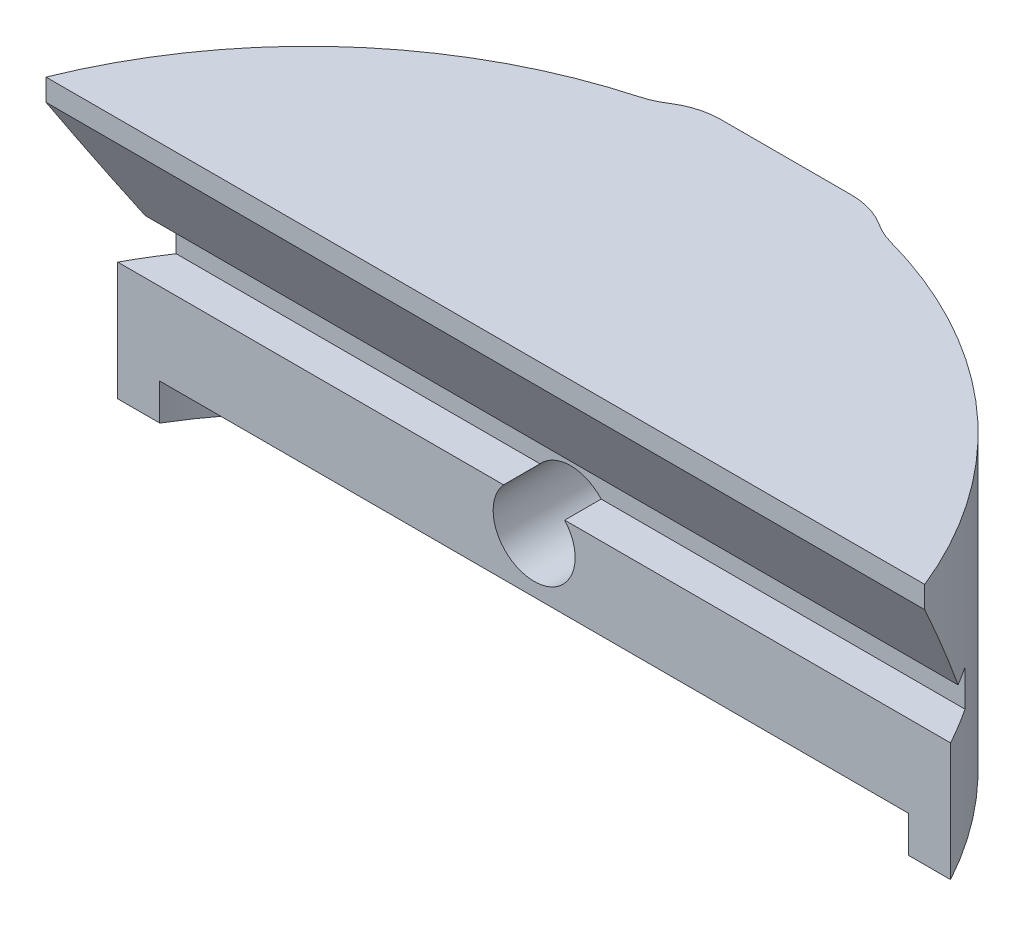
SolidWorks part; units mm, degrees
material "3.1355 (EN-AW 2024)"
ref_plane "Спереди" through (0, 0, 0) normal (0, 0, 1) x (1, 0, 0)
ref_plane "Сверху" through (0, 0, 0) normal (0, 1, 0) x (1, 0, 0)
ref_plane "Справа" through (0, 0, 0) normal (1, 0, 0) x (0, 0, -1)
sketch "Эскиз1" plane through (0, 0, 0) normal (0, 1, 0) x (1, 0, 0)
  circle A0 centre (0, 0) radius 26
  dimension "D1" = 52
extrude "Бобышка-Вытянуть1" add sketch "Эскиз1" along normal blind 14
sketch "Эскиз2" plane through (0, 0, 0) normal (1, 0, 0) x (0, 0, -1)
  line L0 (0, 14) -> (0, 0) construction
  line L1 (26, 14) -> (-26, 14) construction
  line L2 (13.6547, 6) -> (-13.6547, 6)
  line L3 (-13.6547, 6) -> (-9.7287, 12.8)
  line L4 (-9.7287, 12.8) -> (-9.7287, 14)
  line L5 (-9.7287, 14) -> (9.7287, 14)
  line L6 (0, 14) -> (0, 6) construction
  line L7 (13.6547, 6) -> (9.7287, 12.8)
  line L8 (9.7287, 12.8) -> (9.7287, 14)
  line L9 (-12.5, 8) -> (-12.5, 6) construction
  dimension "D1" = 8
  dimension "D2" = 1.2
  dimension "D3" = 60
  dimension "D4" = 13.6547
  dimension "D5" = 9.7287
  dimension "D6" = 2
  dimension "D7" = 12.5
extrude "Вырез-Вытянуть1" cut sketch "Эскиз2" against normal mid plane 60
sketch "Примерка" plane through (0, 0, 0) normal (1, 0, 0) x (0, 0, -1)
  line L0 (13.6547, 6) -> (-13.6547, 6) construction
  line L1 (-12.5, 14) -> (12.5, 14)
  line L2 (-12.5, 14) -> (-12.5, 6)
  line L3 (-12.5, 6) -> (12.5, 6)
  line L4 (12.5, 14) -> (12.5, 6)
  point P6 (0, 6)
  dimension "D1" = 8
  dimension "D2" = 25
sketch "Эскиз5" plane through (0, 0, 0) normal (0, -1, 0) x (1, 0, 0)
  line L2 (-22.1258, -15.6547) -> (22.1258, -15.6547)
  line L3 (-18.1915, -15.6547) -> (18.1915, -15.6547)
  circle A2 centre (0, 0) radius 24
  arc A3 (-18.1915, -15.6547) -> (18.1915, -15.6547) centre (0, 0) ccw
  dimension "D1" = 2
  dimension "D2" = 2
sketch "Эскиз6" plane through (0, 6, 0) normal (0, 1, 0) x (1, 0, 0)
  line L1 (18.4208, 0) -> (-15.4735, 0) construction
  circle A0 centre (0, 0) radius 6 construction
  circle A1 centre (0, 0) radius 12.5 construction
  dimension "D1" = 12
  dimension "D2" = 25
hole_wizard "Цековка для винта с внутренним шестигранником M32" positions "Эскиз14" profile "Эскиз13" counterbore size "M3" standard "Ansi Metric" end condition up to next
sketch "Эскиз14" plane through (0, 6, 0) normal (0, 1, 0) x (1, 0, 0)
  line L0 (18.4208, 0) -> (-15.4735, 0) construction
  circle A0 centre (0, 0) radius 12.5 construction
  circle A1 centre (0, 0) radius 6 construction
  point P0 (-12.5, 0)
  point P6 (12.5, 0)
  point P20 (-6, 0)
  point P24 (6, 0)
sketch "Эскиз13" plane through (-12.5, 6, 0) normal (1, 0, 0) x (0, 0, 1)
  line L0 (0, 0) -> (0, 6)
  line L1 (0, 6) -> (1.7, 6)
  line L3 (1.7, 6) -> (1.7, 3)
  line L4 (1.7, 3) -> (3.3, 3)
  line L5 (3.3, 3) -> (3.3, 0)
  line L7 (3.3, 0) -> (0, 0)
  line L11 (0, -6.35) -> (0, 107.95) construction
  dimension "Диаметр сквозного отверстия" = 3.4
  dimension "Глубина сквозного отверстия" = 6
  dimension "Диаметр цековки" = 6.6
  dimension "Глубина цековки" = 3
sketch "Эскиз12" plane through (0, 0, 0) normal (0, -1, 0) x (1, 0, 0)
  circle A0 centre (0, 0) radius 26 construction
  circle A1 centre (0, 0) radius 26
  circle A3 centre (0, 0) radius 24
  dimension "D1" = 2
extrude "Бобышка-Вытянуть2" add sketch "Эскиз12" along normal blind 2
sketch "Эскиз17" plane through (0, 14, 0) normal (0, 1, 0) x (1, 0, 0)
  line L0 (-24.1112, -9.7287) -> (24.1112, -9.7287) construction
  line L1 (-24.1112, -9.7287) -> (24.1112, -9.7287)
  arc A0 (-24.1112, -9.7287) -> (24.1112, -9.7287) centre (0, 0) ccw construction
  arc A1 (-24.1112, -9.7287) -> (24.1112, -9.7287) centre (0, 0) ccw
extrude "Вырез-Вытянуть4" cut sketch "Эскиз17" against normal up to surface (8 mm away) up to face at (9.25, 6, 0)
fillet "Скругление2" radius 1 4 edges at (9.25, 4.5, -0.5723) (9.25, 4.5, 0.5723) (-9.25, 4.5, 0.5723) (-9.25, 4.5, -0.5723)
sketch "Эскиз18" plane through (0, 0, 0) normal (0, -1, 0) x (1, 0, 0)
  circle A0 centre (0, 0) radius 6
extrude "Вырез-Вытянуть5" cut sketch "Эскиз18" against normal blind 3
sketch "Эскиз19" plane through (0, 6, 0) normal (0, 1, 0) x (1, 0, 0)
  line L0 (-22.3137, -13.3453) -> (22.3137, -13.3453)
  line L1 (-22.1258, 13.6547) -> (22.1258, 13.6547) construction
  arc A0 (-22.1258, 13.6547) -> (22.1258, 13.6547) centre (0, 0) ccw construction
  arc A1 (-22.3137, -13.3453) -> (22.3137, -13.3453) centre (0, 0) ccw
  dimension "D1" = 27
extrude "Вырез-Вытянуть6" cut sketch "Эскиз19" against normal blind 10
sketch "Эскиз21" plane through (0, 0, 13.3453) normal (0, 0, 1) x (1, 0, 0)
  line L0 (0, 0) -> (0, 6) construction
  line L1 (19.9475, 0) -> (-19.9475, 0) construction
  line L2 (22.3137, 6) -> (-22.3137, 6) construction
hole_wizard "Отверстие обработанное метчиком M4x0.71" positions "Эскиз23" profile "Эскиз22" tap size "M4x0.7" standard "Ansi Metric"
sketch "Эскиз23" plane through (0, 0, 13.3453) normal (0, 0, 1) x (1, 0, 0)
  line L0 (0, 0) -> (0, 6) construction
  point P0 (0, 3)
sketch "Эскиз22" plane through (0, 3, 13.3453) normal (1, 0, 0) x (0, -1, 0)
  line L0 (0, 0) -> (0, 12.4914)
  line L1 (0, 12.4914) -> (1.65, 11.5)
  line L2 (1.65, 11.5) -> (1.65, 0)
  line L5 (1.65, 0) -> (0, 0)
  line L10 (0, 12.4914) -> (-1.65, 11.5) construction
  line L11 (0, -6.35) -> (0, 107.95) construction
  dimension "Диаметр сверла" = 3.3
  dimension "Глубина сверла" = 11.5
  dimension "Угол заточки сверла" = 118
cosmetic thread "Отверстие резьбы1" parameters "D1"=8, "D2"=4
sketch "Эскиз20" plane through (0, 0, 13.3453) normal (0, 0, 1) x (1, 0, 0)
  line L0 (0, 3.1198) -> (0, -5.6063) construction
  line L1 (22.3137, 6) -> (-22.3137, 6) construction
  line L2 (-25.2658, 5) -> (25.2658, 5)
  line L3 (-25.2658, 5) -> (-25.2658, -2)
  line L4 (-25.2658, -2) -> (25.2658, -2)
  line L5 (25.2658, 5) -> (25.2658, -2)
  line L6 (-25.2658, 5) -> (25.2658, -2) construction
  line L7 (-25.2658, -2) -> (25.2658, 5) construction
  line L8 (-22.3137, -2) -> (-19.9475, -2) construction
  point P3 (0, 1.5)
  dimension "D1" = 1
extrude "Вырез-Вытянуть7" cut sketch "Эскиз20" against normal blind 2
sketch "Эскиз24" plane through (0, 0, 11.3453) normal (0, 0, 1) x (1, 0, 0)
  line L0 (0, 0) -> (0, -5.889) construction
  line L1 (-21.1491, 0) -> (21.1491, 0) construction
  line L2 (-11.3153, 1) -> (11.3153, 1)
  line L3 (-11.3153, 1) -> (-11.3153, 0)
  line L4 (-11.3153, 0) -> (11.3153, 0)
  line L5 (11.3153, 1) -> (11.3153, 0)
  line L6 (-11.3153, 1) -> (11.3153, 0) construction
  line L7 (-11.3153, 0) -> (11.3153, 1) construction
  point P3 (0, 0.5)
  dimension "D1" = 1
extrude "Бобышка-Вытянуть3" add sketch "Эскиз24" along normal blind 2
ref_plane "Плоскость1" through (26, 0, 0) normal (1, 0, 0) x (0, 0, -1)
sketch "Эскиз25" plane through (26, 0, 0) normal (1, 0, 0) x (0, 0, -1)
  line L0 (13.6547, 6) -> (13.6547, -5.3122) construction
  line L1 (12.4047, -5.3122) -> (-15.3444, -5.3122)
  line L2 (-15.3444, -5.3122) -> (-15.3444, 6)
  line L3 (-15.3444, 6) -> (12.4047, 6)
  line L4 (12.4047, 6) -> (12.4047, -5.3122)
  line L5 (13.6547, 6) -> (-13.3453, 6) construction
  dimension "D1" = 2.5
extrude "Вырез-Вытянуть8" cut sketch "Эскиз25" against normal through all
sketch "Эскиз26" plane through (26, 0, 0) normal (1, 0, 0) x (0, 0, -1)
  line L0 (12.4047, 6.5) -> (14.4047, 6.5)
  line L1 (14.4047, 6.5) -> (14.4047, 4.5)
  line L2 (14.4047, 4.5) -> (12.4047, 4.5)
  line L3 (12.4047, 4.5) -> (12.4047, 6.5)
  line L5 (26, 14) -> (9.7287, 14) construction
  line L7 (12.4047, 6) -> (12.4047, -2) construction
  dimension "D1" = 2
  dimension "D2" = 7.5
  dimension "D3" = 2
extrude "Вырез-Вытянуть10" cut sketch "Эскиз26" against normal through all
sketch "Эскиз27" plane through (0, 14, 0) normal (0, 1, 0) x (1, 0, 0)
  line L0 (0, 26) -> (0, 26.4574) construction
  line L2 (24.1112, 9.7287) -> (-24.1112, 9.7287) construction
  line L3 (-5, 26.2287) -> (5, 26.2287)
  line L4 (-5, 26.2287) -> (-5, 25.5147)
  line L6 (5, 26.2287) -> (5, 25.5147)
  line L7 (-5, 26.2287) -> (5.2086, 22.8067) construction
  line L8 (-6.2536, 22.4564) -> (5, 26.2287) construction
  arc A0 (-5, 25.5147) -> (5, 25.5147) centre (0, 0) cw
  arc A1 (24.1112, 9.7287) -> (-24.1112, 9.7287) centre (0, 0) ccw construction
  point P5 (0, 24.5527)
  point P18 (0, 26.2287)
  dimension "D1" = 10
  dimension "D2" = 16.5
extrude "Бобышка-Вытянуть5" add sketch "Эскиз27" against normal up to surface (16 mm away) up to face at (0, -2, -18.7024)
fillet "Скругление3" radius 4 2 edges at (5, 6, -25.5147) (-5, 6, -25.5147)
fillet "Скругление4" radius 4 2 edges at (5, 6, -26.2287) (-5, 6, -26.2287)
sketch "Эскиз28" plane through (0, 0, -26.2287) normal (0, 0, -1) x (-1, 0, 0)
  line L0 (0, -2) -> (0, 4.3259) construction
  line L1 (-3.5784, -2) -> (3.5784, -2) construction
  point P5 (0, 3)
  dimension "D1" = 5
hole_wizard "Отверстие с зазором M41" positions "Эскиз30" profile "Эскиз29" hole size "M4" standard "Ansi Metric" end condition through all
sketch "Эскиз30" plane through (0, 0, -26.2287) normal (0, 0, -1) x (-1, 0, 0)
  point P0 (0, 3)
sketch "Эскиз29" plane through (0, 3, -26.2287) normal (1, 0, 0) x (0, 1, 0)
  line L0 (0, 0) -> (0, 16.5)
  line L1 (0, 16.5) -> (2.25, 16.5)
  line L2 (2.25, 16.5) -> (2.25, 0)
  line L5 (2.25, 0) -> (0, 0)
  line L11 (0, -6.35) -> (0, 107.95) construction
  dimension "Диаметр сквозного отверстия" = 4.5
  dimension "Глубина сквозного отверстия" = 16.5
